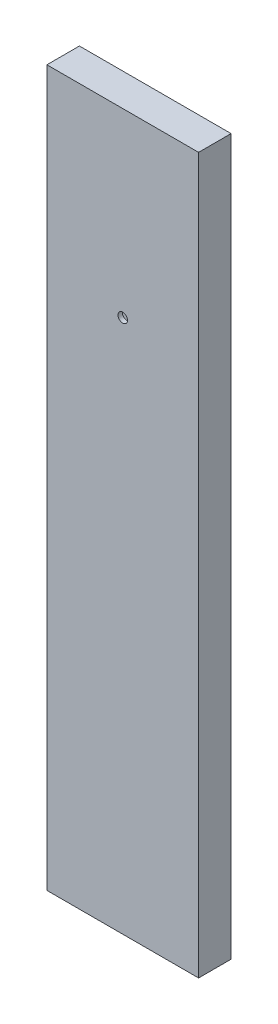
SolidWorks part; units mm, degrees
ref_plane "Front Plane" through (0, 0, 0) normal (0, 0, 1) x (1, 0, 0)
ref_plane "Top Plane" through (0, 0, 0) normal (0, 1, 0) x (1, 0, 0)
ref_plane "Right Plane" through (0, 0, 0) normal (1, 0, 0) x (0, 0, -1)
sketch "Sketch1" plane through (0, 0, 0) normal (0, 1, 0) x (1, 0, 0)
  line L1 (0, 0) -> (88.9, 0)
  line L2 (0, 0) -> (0, 19.05)
  line L3 (0, 19.05) -> (88.9, 19.05)
  line L4 (88.9, 0) -> (88.9, 19.05)
  dimension "D1" = 19.05
  dimension "D2" = 88.9
extrude "Boss-Extrude1" add sketch "Sketch1" along normal blind 419.1
sketch "Sketch2" plane through (0, 0, 0) normal (0, 0, 1) x (1, 0, 0)
  line L0 (-349.25, 406.4) -> (49.4536, 406.4) construction
  line L1 (-349.25, 406.4) -> (44.45, 312.9704) construction
  line L2 (44.45, 419.1) -> (44.45, 119.6601) construction
  line L3 (0, 419.1) -> (88.9, 419.1) construction
  circle A0 centre (-349.25, 406.4) radius 2.7781 construction
  circle A1 centre (-349.25, 406.4) radius 2.7781
  circle A2 centre (44.45, 312.9704) radius 2.7781
  point P10 (0, 0)
  dimension "D1" = 13.35
extrude "Cut-Extrude1" cut sketch "Sketch2" against normal blind 2.54
